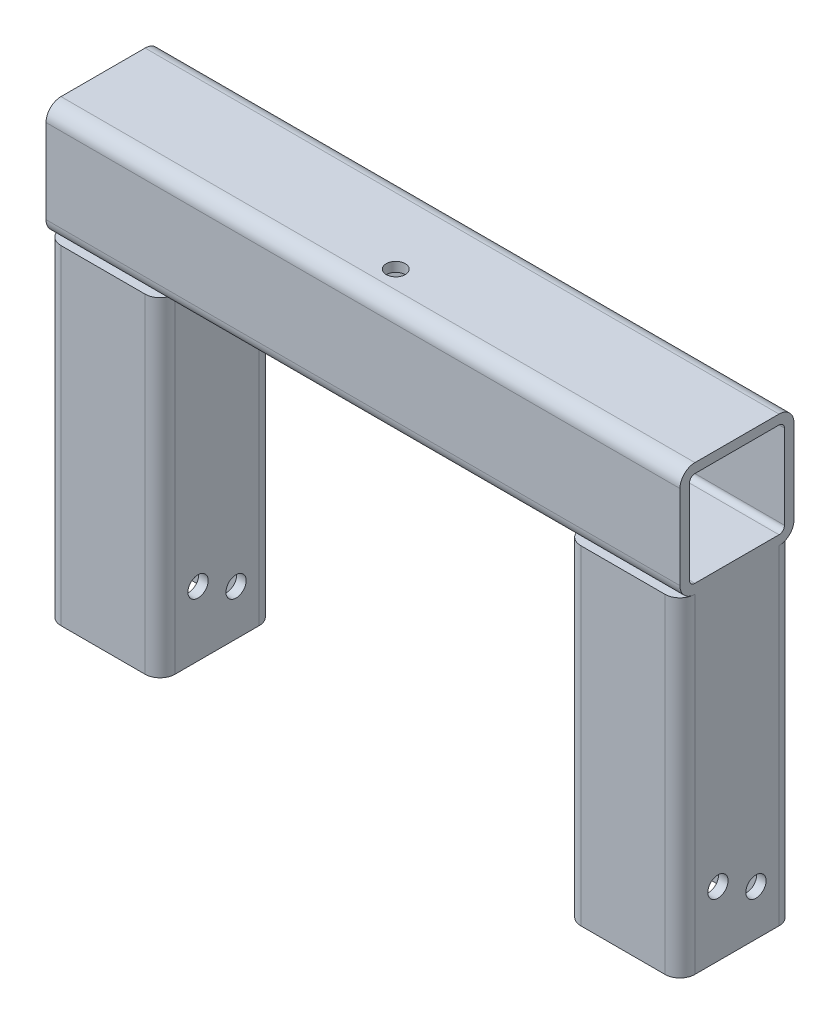
SolidWorks part; units mm, degrees
ref_plane "Front Plane" through (0, 0, 0) normal (0, 0, 1) x (1, 0, 0)
ref_plane "Top Plane" through (0, 0, 0) normal (0, 1, 0) x (1, 0, 0)
ref_plane "Right Plane" through (0, 0, 0) normal (1, 0, 0) x (0, 0, -1)
sketch "Sketch1" plane through (0, 0, 0) normal (0, 1, 0) x (1, 0, 0)
  line L0 (-14.05, 19.05) -> (14.05, 19.05)
  line L1 (19.05, 14.05) -> (19.05, -14.05)
  line L2 (-15.875, 14.05) -> (-15.875, -14.05)
  line L3 (-14.05, -15.875) -> (14.05, -15.875)
  line L4 (14.05, -19.05) -> (-14.05, -19.05)
  line L5 (-19.05, -14.05) -> (-19.05, 14.05)
  line L6 (0, 19.05) -> (0, -19.05) construction
  line L7 (-19.05, 0) -> (19.05, 0) construction
  line L8 (15.875, -14.05) -> (15.875, 14.05)
  line L9 (14.05, 15.875) -> (-14.05, 15.875)
  line L10 (0, 15.875) -> (0, -15.875) construction
  line L11 (-15.875, 0) -> (15.875, 0) construction
  arc A0 (14.05, 19.05) -> (19.05, 14.05) centre (14.05, 14.05) cw
  arc A1 (19.05, -14.05) -> (14.05, -19.05) centre (14.05, -14.05) cw
  arc A2 (-14.05, -19.05) -> (-19.05, -14.05) centre (-14.05, -14.05) cw
  arc A3 (-19.05, 14.05) -> (-14.05, 19.05) centre (-14.05, 14.05) cw
  arc A4 (-15.875, -14.05) -> (-14.05, -15.875) centre (-14.05, -14.05) ccw
  arc A5 (14.05, -15.875) -> (15.875, -14.05) centre (14.05, -14.05) ccw
  arc A6 (15.875, 14.05) -> (14.05, 15.875) centre (14.05, 14.05) ccw
  arc A7 (-14.05, 15.875) -> (-15.875, 14.05) centre (-14.05, 14.05) ccw
  point P33 (0, 0)
  dimension "D1" = 5
  dimension "D2" = 3.175
  dimension "D3" = 38.1
extrude "Boss-Extrude1" add sketch "Sketch1" along normal blind 110
ref_plane "Plane1" through (86.85, 0, 0) normal (1, 0, 0) x (0, 0, -1)
mirror "Mirror2" about plane through (86.85, 0, 0) normal (1, 0, 0) of bodies 101
sketch "Sketch2" plane through (86.85, 0, 0) normal (1, 0, 0) x (0, 0, -1)
  line L0 (-14.05, 148.1) -> (14.05, 148.1)
  line L1 (19.05, 143.1) -> (19.05, 115)
  line L2 (-15.875, 143.1) -> (-15.875, 115)
  line L3 (-14.05, 113.175) -> (14.05, 113.175)
  line L4 (14.05, 110) -> (-14.05, 110)
  line L5 (-19.05, 115) -> (-19.05, 143.1)
  line L6 (0, 148.1) -> (0, 110) construction
  line L7 (-19.05, 129.05) -> (19.05, 129.05) construction
  line L8 (15.875, 115) -> (15.875, 143.1)
  line L9 (14.05, 144.925) -> (-14.05, 144.925)
  line L10 (0, 144.925) -> (0, 113.175) construction
  line L11 (-15.875, 129.05) -> (15.875, 129.05) construction
  line L12 (0, 55) -> (0, -55) construction
  line L13 (14.05, 110) -> (-14.05, 110) construction
  arc A0 (14.05, 148.1) -> (19.05, 143.1) centre (14.05, 143.1) cw
  arc A1 (19.05, 115) -> (14.05, 110) centre (14.05, 115) cw
  arc A2 (-14.05, 110) -> (-19.05, 115) centre (-14.05, 115) cw
  arc A3 (-19.05, 143.1) -> (-14.05, 148.1) centre (-14.05, 143.1) cw
  arc A4 (-15.875, 115) -> (-14.05, 113.175) centre (-14.05, 115) ccw
  arc A5 (14.05, 113.175) -> (15.875, 115) centre (14.05, 115) ccw
  arc A6 (15.875, 143.1) -> (14.05, 144.925) centre (14.05, 143.1) ccw
  arc A7 (-14.05, 144.925) -> (-15.875, 143.1) centre (-14.05, 143.1) ccw
  dimension "D1" = 5
  dimension "D2" = 3.175
  dimension "D3" = 38.1
extrude "Boss-Extrude2" add sketch "Sketch2" along normal up to surface (105.9 mm away) and the other way up to surface (105.9 mm away) up to face at (192.75, 55, 0) other way up to face at (-19.05, 55, 0)
sketch "Sketch3" plane through (0, 110, 0) normal (0, -1, 0) x (1, 0, 0)
  circle A0 centre (86.8, 8.05) radius 3.175
extrude "Cut-Extrude1" cut sketch "Sketch3" against normal up to surface (38.1 mm away) up to face at (86.85, 148.1, 0)
hole_wizard "1/4 Clearance Hole1" positions "Sketch4" profile "Sketch5" hole size "1/4" standard "ANSI Inch" end condition through all
sketch "Sketch4" plane through (-19.05, 0, 0) normal (-1, 0, 0) x (0, 0, 1)
  line L0 (-14.05, 0) -> (14.05, 0) construction
  point P0 (-6.35, 15.24)
  point P2 (6.35, 21.59)
  point P7 (0, 0)
  dimension "D1" = 15.24
  dimension "D2" = 12.7
  dimension "D3" = 6.35
  dimension "D4" = 6.35
sketch "Sketch5" plane through (-19.05, 15.24, -6.35) normal (0, 1, 0) x (0, 0, 1)
  line L0 (0, 0) -> (0, 211.8)
  line L1 (0, 211.8) -> (3.3782, 211.8)
  line L2 (3.3782, 211.8) -> (3.3782, 0)
  line L5 (3.3782, 0) -> (0, 0)
  line L11 (0, -6.35) -> (0, 107.95) construction
  dimension "Thru Hole Dia." = 6.7564
  dimension "Thru Hole Depth" = 211.8
